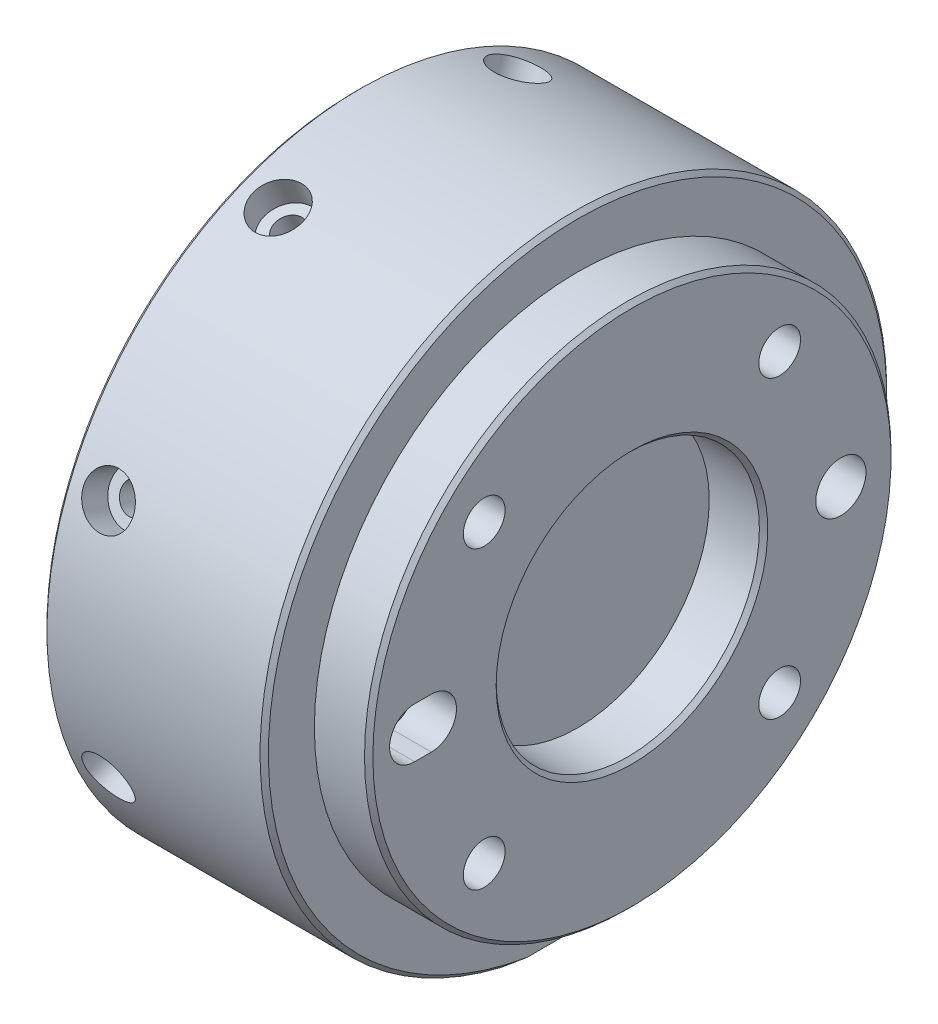
SolidWorks part; units mm, degrees
material "6061"
ref_plane "前视" through (0, 0, 0) normal (0, 0, 1) x (1, 0, 0)
ref_plane "上视" through (0, 0, 0) normal (0, 1, 0) x (1, 0, 0)
ref_plane "右视" through (0, 0, 0) normal (1, 0, 0) x (0, 0, -1)
sketch "草图1" plane through (0, 0, 0) normal (0, 0, 1) x (1, 0, 0)
  line L0 (0, 0) -> (69.0702, 0) construction
  line L1 (0, 31) -> (0, 37.5)
  line L2 (0, 37.5) -> (26.5, 37.5)
  line L3 (26.5, 37.5) -> (26.5, 31.5)
  line L4 (26.5, 31.5) -> (33, 31.5)
  line L5 (33, 31.5) -> (33, 15.75)
  line L6 (33, 15.75) -> (26.5, 15.75)
  line L7 (26.5, 15.75) -> (26.5, 0)
  line L8 (26.5, 0) -> (22, 0)
  line L9 (22, 0) -> (22, 30)
  line L10 (22, 30) -> (10, 30)
  line L11 (10, 30) -> (10, 31)
  line L12 (10, 31) -> (0, 31)
  dimension "D1" = 75
  dimension "D2" = 33
  dimension "D3" = 26.5
  dimension "D4" = 62
  dimension "D5" = 60
  dimension "D6" = 22
  dimension "D7" = 10
  dimension "D8" = 63
  dimension "D9" = 31.5
  dimension "D10" = 6.5
revolve "旋转1" add sketch "草图1" angle 360 about L0
hole_wizard "M6 螺纹孔1" positions "草图2" profile "草图3" tap size "M6" standard "GB"
sketch "草图2" plane through (33, 0, 0) normal (1, 0, 0) x (0, 0, -1)
  line L0 (0, 24.0966) -> (0, 0) construction
  line L1 (0, 0) -> (46.0777, 0) construction
  line L3 (0, 0) -> (17.6777, 17.6777) construction
  point P0 (17.6777, 17.6777)
  point P9 (17.6777, -17.6777)
  point P10 (-17.6777, -17.6777)
  point P11 (-17.6777, 17.6777)
  dimension "D1" = 25
  dimension "D2" = 45
sketch "草图3" plane through (33, 17.6777, -17.6777) normal (0, 1, 0) x (0, 0, -1)
  line L0 (0, 0) -> (0, 10.5022)
  line L1 (0, 10.5022) -> (2.5, 9)
  line L2 (2.5, 9) -> (2.5, 0)
  line L5 (2.5, 0) -> (0, 0)
  line L10 (0, 10.5022) -> (-2.5, 9) construction
  line L11 (0, -6.35) -> (0, 107.95) construction
  dimension "螺纹孔钻头直径" = 5
  dimension "螺纹孔钻头深度" = 9
  dimension "导头角度" = 118
cosmetic thread "孔螺蚊线1" parameters "D1"=7, "D2"=6
cosmetic thread "孔螺蚊线2" parameters "D1"=7, "D2"=6
cosmetic thread "孔螺蚊线3" parameters "D1"=7, "D2"=6
cosmetic thread "孔螺蚊线4" parameters "D1"=7, "D2"=6
sketch "草图4" plane through (33, 0, 0) normal (1, 0, 0) x (0, 0, -1)
  line L0 (0, 22.3423) -> (0, 0) construction
  line L1 (0, 0) -> (25, 0) construction
  line L2 (-26, 0) -> (-24, 0) construction
  line L3 (-26, 3) -> (-24, 3)
  line L4 (-26, -3) -> (-24, -3)
  circle A0 centre (25, 0) radius 3
  arc A1 (-26, 3) -> (-26, -3) centre (-26, 0) ccw
  arc A2 (-24, -3) -> (-24, 3) centre (-24, 0) ccw
  point P7 (-25, 0)
  point P12 (0, 0)
  point P13 (0, 0)
  dimension "D1" = 6
  dimension "D2" = 25
  dimension "D3" = 6
  dimension "D4" = 25
  dimension "D5" = 2
extrude "切除-拉伸1" cut sketch "草图4" against normal blind 5
hole_wizard "M12x1.25 螺纹孔1" positions "草图5" profile "草图6" tap size "M12x1.25" standard "GB" end condition through all
sketch "草图5" plane through (0, 0, 0) normal (0, 1, 0) x (1, 0, 0)
  point P0 (16.5, 0)
  point P6 (0, 0)
  dimension "D1" = 16.5
sketch "草图6" plane through (16.5, 0, 0) normal (1, 0, 0) x (0, 0, 1)
  line L0 (0, 0) -> (0, 37.5)
  line L1 (0, 37.5) -> (5.25, 37.5)
  line L2 (5.25, 37.5) -> (5.25, 0)
  line L5 (5.25, 0) -> (0, 0)
  line L11 (0, -6.35) -> (0, 107.95) construction
  dimension "通孔螺纹孔钻头直径" = 10.5
  dimension "通孔螺纹孔钻头深度" = 37.5
cosmetic thread "孔螺蚊线5" parameters "D2"=12
sketch "草图7" plane through (0, 0, 0) normal (0, 1, 0) x (1, 0, 0)
  line L0 (0, -37.5) -> (26.5, -37.5) construction
  line L1 (26.5, 37.5) -> (8.5, 37.5)
  line L2 (26.5, 37.5) -> (26.5, -37.5)
  line L3 (26.5, -37.5) -> (8.5, -37.5)
  line L4 (8.5, 37.5) -> (8.5, -37.5)
  dimension "D1" = 8.5
extrude "切除-拉伸2" cut sketch "草图7" against normal through all from offset 36.5 offset against normal yes
ref_axis "基准轴1" through (26.5, 0, 0) along (-1, 0, 0)
ref_plane "基准面2" through (0, 0, 0) normal (0, 0.9239, 0.3827) x (-1, 0, 0)
ref_plane "基准面3" through (0, 34.6455, 14.3506) normal (0, 0.9239, 0.3827) x (-1, 0, 0)
hole_wizard "打孔尺寸(%根据)内六角圆柱头螺钉的类型2" positions "草图8" profile "草图9" counterbore size "M3" standard "GB" end condition up to next
sketch "草图8" plane through (0, 34.6455, 14.3506) normal (0, 0.9239, 0.3827) x (-1, 0, 0)
  point P0 (-5, 0)
  dimension "D1" = 5
sketch "草图9" plane through (5, 34.6455, 14.3506) normal (1, 0, 0) x (0, -0.3827, 0.9239)
  line L0 (0, 0) -> (0, 78.0048)
  line L1 (0, 78.0048) -> (1.7, 78.0048)
  line L3 (1.7, 78.0048) -> (1.7, 3.4)
  line L4 (1.7, 3.4) -> (3, 3.4)
  line L5 (3, 3.4) -> (3, 0)
  line L7 (3, 0) -> (0, 0)
  line L11 (0, -6.35) -> (0, 107.95) construction
  dimension "通孔孔直径" = 3.4
  dimension "通孔孔深度" = 78.0048
  dimension "柱形沉头孔直径" = 6
  dimension "柱形沉头孔深度" = 3.4
pattern_circular "阵列(圆周)1" count 8 over 360 about axis through (0, 0, 0) along (-1, 0, 0) of "打孔尺寸(%根据)内六角圆柱头螺钉的类型2" reverse direction yes
chamfer "倒角1" distance 0.5 angle 45 6 edges at (10, 0, 30) (33, 0, 15.75) (33, 0, 31.5) (26.5, 37.5, 0) (0, 0, 31) (0, 0, 37.5)
